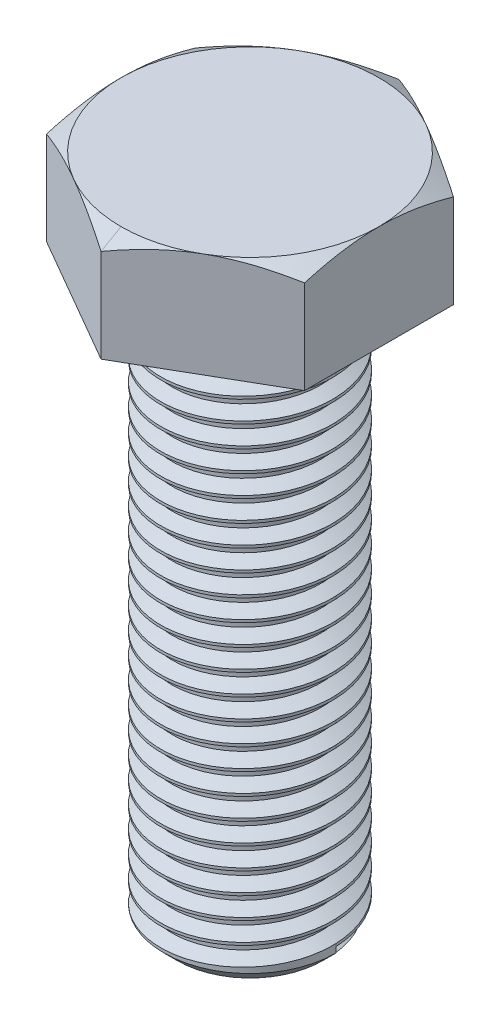
SolidWorks part; units mm, degrees
ref_plane "Front Plane" through (0, 0, 0) normal (0, 0, 1) x (1, 0, 0)
ref_plane "Top Plane" through (0, 0, 0) normal (0, 1, 0) x (1, 0, 0)
ref_plane "Right Plane" through (0, 0, 0) normal (1, 0, 0) x (0, 0, -1)
sketch "Sketch1" plane through (0, 0, 0) normal (0, 1, 0) x (1, 0, 0)
  circle A0 centre (0, 0) radius 12.7
  dimension "D1" = 25.4
extrude "Boss-Extrude1" add sketch "Sketch1" along normal blind 82.55
chamfer "Chamfer1" distance 1.9476 angle 45 1 edges at (0, 0, 12.7)
thread "Thread1" pitch 3.175 method cut profile "Thread Profile1" start angle 0, offset 0, length 79.375, pitch 3.175, diameter 25.4
ref_plane "Plane1" through (12.7, 0, 0) normal (0, 0, 1) x (1, 0, 0)
sketch "Thread Profile1" plane through (12.7, 0, 0) normal (0, 0, 1) x (1, 0, 0)
  line L0 (0, 0) -> (0, 3.175) construction
  line L11 (0, 0) -> (0, 2.7781)
  line L12 (0, 2.7781) -> (-1.7185, 1.7859)
  line L13 (-1.7185, 1.7859) -> (-1.7185, 0.9922)
  line L15 (-1.7185, 0.9922) -> (0, 0)
  line L17 (-1.7185, 1.3891) -> (0, 1.3891) construction
  point P2 (0, 0)
  dimension "Pitch" = 3.175
  dimension "Profile_Angle" = 60
  dimension "Profile_Land" = 0.7937
  dimension "Profile_Height" = 1.7185
sketch "Sketch5" plane through (0, 82.55, 0) normal (0, 1, 0) x (1, 0, 0)
  line L1 (0, -21.997) -> (19.05, -10.9985)
  line L2 (19.05, -10.9985) -> (19.05, 10.9985)
  line L3 (19.05, 10.9985) -> (0, 21.997)
  line L4 (0, 21.997) -> (-19.05, 10.9985)
  line L5 (-19.05, 10.9985) -> (-19.05, -10.9985)
  line L6 (-19.05, -10.9985) -> (0, -21.997)
  circle A0 centre (0, 0) radius 19.05 construction
  point P1 (0, 0)
  dimension "D1" = 38.1
extrude "Boss-Extrude2" add sketch "Sketch5" along normal blind 15.4781
sketch "Sketch6" plane through (0, 98.0281, 0) normal (0, 1, 0) x (1, 0, 0)
  line L0 (19.05, -10.9985) -> (19.05, 10.9985) construction
  circle A0 centre (0, 0) radius 19.05
sketch "Sketch7" plane through (0, 0, 0) normal (1, 0, 0) x (0, 0, -1)
  line L0 (-19.05, 98.0281) -> (-21.997, 98.0281)
  line L1 (19.05, 98.0281) -> (-19.05, 98.0281) construction
  line L2 (-21.997, 98.0281) -> (-10.9985, 98.0281) construction
  line L3 (-21.997, 98.0281) -> (-21.997, 96.3266)
  line L4 (-21.997, 96.3266) -> (-19.05, 98.0281)
  line L5 (-21.997, 98.0281) -> (-21.997, 82.55) construction
  point P6 (0, 0)
  dimension "D1" = 30
sweep "Cut-Sweep1" cut profiles "Sketch7" path "Sketch6"
